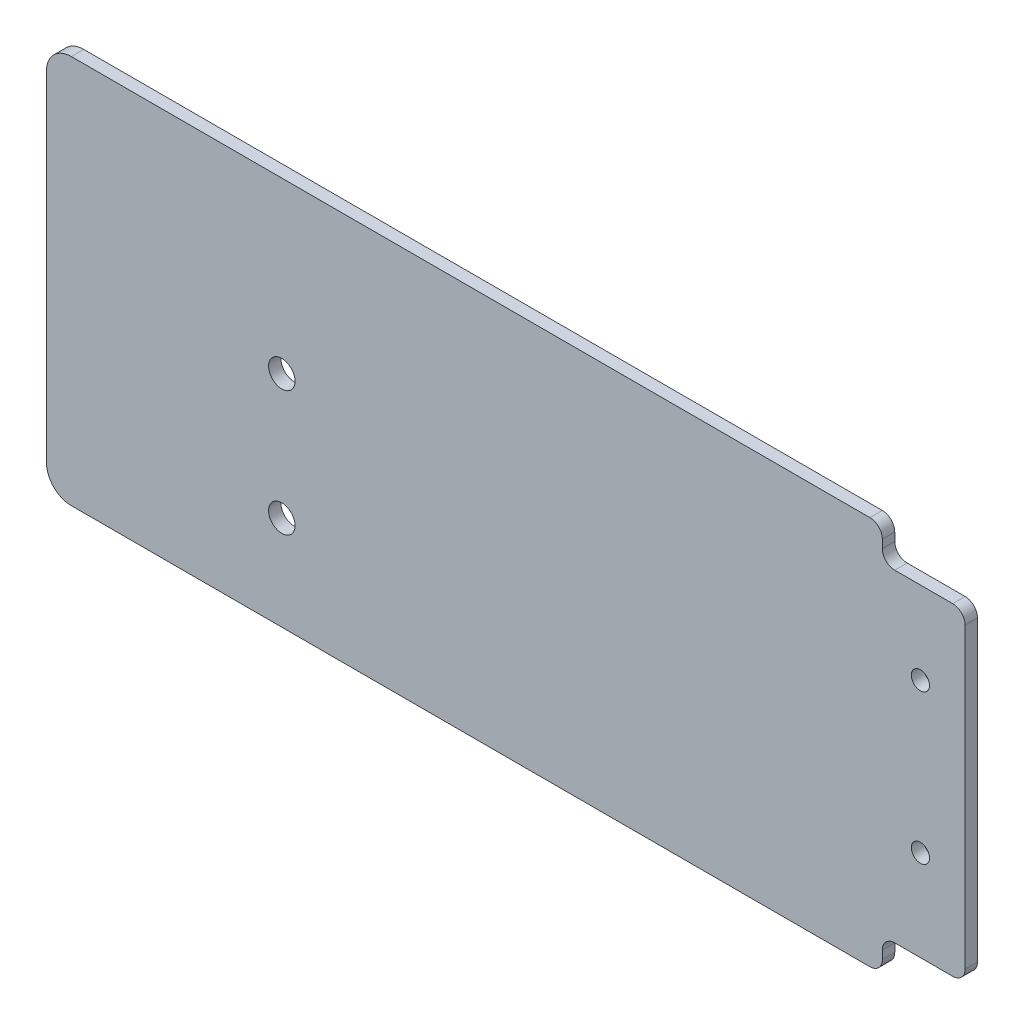
SolidWorks part; units mm, degrees
note: '?' marks a value the reader was unsure of.
ref_plane "Front Plane" through (0, 0, 0) normal (0, 0, 1) x (1, 0, 0)
ref_plane "Top Plane" through (0, 0, 0) normal (0, 1, 0) x (1, 0, 0)
ref_plane "Right Plane" through (0, 0, 0) normal (1, 0, 0) x (0, 0, -1)
ref_axis "Axis1" through (0, 0, -88.99) along (0, 0, 1)?
ref_axis "Axis2" through (0, -55, 0) along (0, 1, 0)?
ref_axis "Axis3" through (-88.99, 0, 0) along (1, 0, 0)?
sketch "Sketch1" plane through (0, 0, 0) normal (0, 0, 1) x (1, 0, 0)
  line L1 (3, -23.5) -> (109, -23.5)
  line L2 (0, -20.5) -> (0, 20.5)
  line L3 (3, 23.5) -> (109, 23.5)
  line L4 (111, -21.5) -> (111, 21.5)
  arc A0 (3, -23.5) -> (0, -20.5) centre (3, -20.5) cw
  arc A1 (0, 20.5) -> (3, 23.5) centre (3, 20.5) cw
  arc A2 (109, -23.5) -> (111, -21.5) centre (109, -21.5) ccw
  arc A3 (109, 23.5) -> (111, 21.5) centre (109, 21.5) cw
  point P4 (0, 0)
  point P8 (0, -23.5)
  point P11 (0, 23.5)
  point P16 (111, 23.5)
  dimension "D3" = 3
  dimension "D4" = 2
  dimension "D1" = 47
  dimension "D2" = 111
extrude "Boss-Extrude1" add sketch "Sketch1" along normal blind 1.5
sketch "Sketch2" plane through (0, 0, 0) normal (0, 0, -1) x (-1, 0, 0)
  line L0 (-101, 23.5) -> (-101, 19.5)
  line L1 (-101, 19.5) -> (-111, 19.5)
  line L2 (-111, 0) -> (0, 0) construction
  line L3 (-101, -19.5) -> (-111, -19.5)
  line L4 (0, -20.5) -> (0, 20.5)
  line L5 (-3, 23.5) -> (-109, 23.5)
  line L6 (-111, 21.5) -> (-111, -21.5)
  line L7 (-109, -23.5) -> (-3, -23.5)
  line L8 (0, -20.5) -> (0, 20.5)
  line L9 (-3, 23.5) -> (-109, 23.5)
  line L10 (-111, 21.5) -> (-111, -21.5)
  line L11 (-109, -23.5) -> (-3, -23.5)
  line L12 (-101, -23.5) -> (-101, -19.5)
  arc A4 (-3, -23.5) -> (0, -20.5) centre (-3, -20.5) ccw
  arc A5 (0, 20.5) -> (-3, 23.5) centre (-3, 20.5) ccw
  arc A6 (-109, 23.5) -> (-111, 21.5) centre (-109, 21.5) ccw
  arc A7 (-111, -21.5) -> (-109, -23.5) centre (-109, -21.5) ccw
  arc A8 (-3, -23.5) -> (0, -20.5) centre (-3, -20.5) ccw
  arc A9 (0, 20.5) -> (-3, 23.5) centre (-3, 20.5) ccw
  arc A10 (-109, 23.5) -> (-111, 21.5) centre (-109, 21.5) ccw
  arc A11 (-111, -21.5) -> (-109, -23.5) centre (-109, -21.5) ccw
  line M12 (-3, 23.5) -> (-109, 23.5)
  arc M13 (-109, 23.5) -> (-111, 21.5) centre (-109, 21.5) ccw
  line M14 (-111, 21.5) -> (-111, -21.5)
  arc M15 (-111, -21.5) -> (-109, -23.5) centre (-109, -21.5) ccw
  line M16 (-109, -23.5) -> (-3, -23.5)
  dimension "D2" = 39
  dimension "D3" = 10
  dimension "D1" = 0
extrude "Cut-Extrude1" cut sketch "Sketch2" against normal through all contours L1 L0 M12 M13 M14 | L12 L3 M16 M14 M15
fillet "Fillet1" radius 1.5 6 edges at (101, -23.5, 0.75) (101, -19.5, 0.75) (111, -19.5, 0.75) (111, 19.5, 0.75) (101, 19.5, 0.75) (101, 23.5, 0.75)
hole_wizard "M3 Clearance Hole1" positions "Sketch4" profile "Sketch3" hole size "M3" standard "ANSI Metric" end condition through all
sketch "Sketch4" plane through (0, 0, 1.5) normal (0, 0, 1) x (1, 0, 0)
  line L0 (111, 0.5) -> (0, 0.5) construction
  line L1 (111, -18) -> (111, 18) construction
  line L2 (0, 20.5) -> (0, -20.5) construction
  line L3 (111, -18) -> (111, 18) construction
  circle A0 centre (105.6, 9.525) radius 1
  circle A1 centre (105.6, -8.525) radius 1
  point P20 (28.437, 3.0309)
  point P22 (28.437, -12.0821)
  dimension "D8" = 5.4
  dimension "D6" = 2
  dimension "D1" = 6.4941
  dimension "D3" = 0.5
  dimension "D4" = 15.113
  dimension "D5" = 77.163
  dimension "D7" = 18.05
sketch "Sketch3" plane through (28.437, 3.0309, 1.5) normal (1, 0, 0) x (0, -1, 0)
  line L0 (0, 0) -> (0, 1.5)
  line L1 (0, 1.5) -> (1.6, 1.5)
  line L2 (1.6, 1.5) -> (1.6, 0)
  line L5 (1.6, 0) -> (0, 0)
  line L11 (0, -6.35) -> (0, 107.95) construction
  dimension "Thru Hole Dia." = 3.2
  dimension "Thru Hole Depth" = 1.5
hole_wizard "M3 Clearance Hole2" [suppressed] positions "Sketch7" profile "Sketch6" hole size "M3" standard "ANSI Metric"
sketch "Sketch7" plane through (0, 0, 1.5) normal (0, 0, 1) x (1, 0, 0)
  line L0 (0, -0.5) -> (111, -0.5) construction
  line L1 (0, 20.5) -> (0, -20.5) construction
  line L2 (111, -18) -> (111, 18) construction
  circle A2 centre (105.6, -9.525) radius 1
  circle A3 centre (105.6, 8.525) radius 1
  point P13 (6.0027, 12.1439)
  point P15 (6.0027, -2.9691)
  dimension "D2" = 2
  dimension "D1" = 0.5
  dimension "D4" = 15.113
  dimension "D5" = 100.6623
  dimension "D6" = 21.6689
  dimension "D7" = 18.05
  dimension "D8" = 5.4
sketch "Sketch6" plane through (6.0027, 12.1439, 1.5) normal (1, 0, 0) x (0, -1, 0)
  line L0 (0, 0) -> (0, 1.5)
  line L1 (0, 1.5) -> (1.6, 1.5)
  line L2 (1.6, 1.5) -> (1.6, 0)
  line L5 (1.6, 0) -> (0, 0)
  line L11 (0, -6.35) -> (0, 107.95) construction
  dimension "Thru Hole Dia." = 3.2
  dimension "Thru Hole Depth" = 1.5
hole_wizard "M2 Clearance Hole1" [suppressed] positions "Sketch9" profile "Sketch8" hole size "M2" standard "ANSI Metric"
sketch "Sketch9" plane through (0, 0, 1.5) normal (0, 0, 1) x (1, 0, 0)
  point P0 (105.6, 8.525)
  point P2 (105.6, -9.525)
sketch "Sketch8" plane through (105.6, 8.525, 1.5) normal (1, 0, 0) x (0, -1, 0)
  line L0 (0, 0) -> (0, 1.5)
  line L1 (0, 1.5) -> (1.1, 1.5)
  line L2 (1.1, 1.5) -> (1.1, 0)
  line L5 (1.1, 0) -> (0, 0)
  line L11 (0, -6.35) -> (0, 107.95) construction
  dimension "Thru Hole Dia." = 2.2
  dimension "Thru Hole Depth" = 1.5
hole_wizard "M2 Clearance Hole2" positions "Sketch11" profile "Sketch10" hole size "M2" standard "ANSI Metric" end condition up to next
sketch "Sketch11" plane through (0, 0, 1.5) normal (0, 0, 1) x (1, 0, 0)
  point P0 (105.6, 9.525)
  point P3 (105.6, -8.525)
sketch "Sketch10" plane through (105.6, 9.525, 1.5) normal (1, 0, 0) x (0, -1, 0)
  line L0 (0, 0) -> (0, 1.5)
  line L1 (0, 1.5) -> (1.1, 1.5)
  line L2 (1.1, 1.5) -> (1.1, 0)
  line L5 (1.1, 0) -> (0, 0)
  line L11 (0, -6.35) -> (0, 107.95) construction
  dimension "Thru Hole Dia." = 2.2
  dimension "Thru Hole Depth" = 1.5
